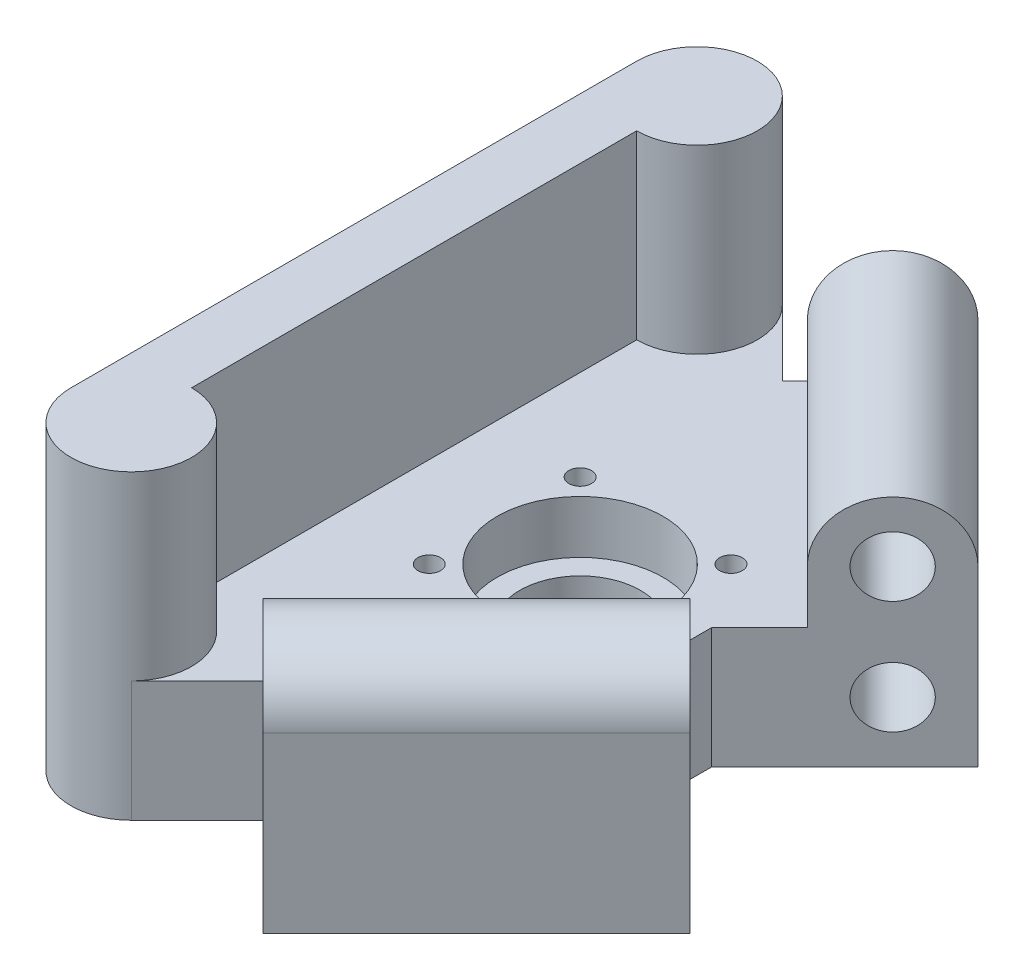
SolidWorks part; units mm, degrees
material "ABS"
ref_plane "Front Plane" through (0, 0, 0) normal (0, 0, 1) x (1, 0, 0)
ref_plane "Top Plane" through (0, 0, 0) normal (0, 1, 0) x (1, 0, 0)
ref_plane "Right Plane" through (0, 0, 0) normal (1, 0, 0) x (0, 0, -1)
sketch "Sketch1" plane through (0, 0, 0) normal (0, 1, 0) x (1, 0, 0)
  line L0 (-386.3027, 0) -> (412.614, 0) construction
  line L1 (0, -323.8826) -> (0, 265.8262) construction
  line L2 (0, 251.091) -> (251.091, 0)
  line L3 (160, 0) -> (80, 138.5641)
  line L4 (160, 0) -> (0, 0)
  line L5 (0, 239.7773) -> (239.7773, 0)
  line L6 (196.4046, 34.4091) -> (187.6569, 43.1569)
  line L9 (174, 0) -> (174, 37.5)
  line L11 (196.4046, 34.4091) -> (209.3717, 47.3762)
  line L12 (209.3717, 47.3762) -> (237.6559, 19.0919)
  line L13 (237.6559, 19.0919) -> (220, 1.4359)
  line L14 (220, 1.4359) -> (220, -1.4359)
  line L15 (237.6559, -19.0919) -> (220, -1.4359)
  line L16 (209.3717, -47.3762) -> (237.6559, -19.0919)
  line L17 (196.4046, -34.4091) -> (209.3717, -47.3762)
  line L18 (187.6569, -43.1569) -> (196.4046, -34.4091)
  line L19 (174, 0) -> (174, -37.5)
  circle A0 centre (0, 0) radius 160
  circle A6 centre (204, 0) radius 11
  circle A7 centre (182, 37.5) radius 4
  circle A8 centre (80, 138.5641) radius 15
  circle A9 centre (194, 10) radius 1.5
  circle A10 centre (214, 10) radius 1.5
  circle A11 centre (214, -10) radius 1.5
  circle A12 centre (194, -10) radius 1.5
  arc A14 (174, 37.5) -> (187.6569, 43.1569) centre (182, 37.5) cw
  circle A16 centre (182, -37.5) radius 4
  arc A17 (174, -37.5) -> (187.6569, -43.1569) centre (182, -37.5) ccw
  circle A21 centre (204, 0) radius 8
  point P53 (220, 0)
  point P65 (144, 0)
  dimension "D1" = 320
  dimension "D10" = 22
  dimension "D13" = 30
  dimension "D11" = 8
  dimension "D14" = 8
  dimension "D18" = 3
  dimension "D28" = 8
  dimension "D34" = 16
  dimension "D8" = 45
  dimension "D9" = 160
  dimension "D12" = 37.5
  dimension "D15" = 15
  dimension "D16" = 44
  dimension "D17" = 22
  dimension "D19" = 10
  dimension "D20" = 10
  dimension "D26" = 8
  dimension "D29" = 4
  dimension "D31" = 16
  dimension "D32" = 40
  dimension "D21" = 2
  dimension "D22" = 2
extrude "Boss-Extrude1" add sketch "Sketch1" along normal blind 16 contours L19 A17 L18 L17 L16 L15 L14 L13 L5 L11 A14 L9 A0 A16 A12 A11 A10 A9 A7 A6 | L13 L2 L11 L5 | L13 L12 L11 L2 | A7 | A16 region at (222.0996, 0, -31.8198) region at (217.857, 0, -27.5772) region at (214.2324, 0, -23.9526) region at (182, 0, -37.5) region at (182, 0, 37.5)
extrude "Boss-Extrude2" add sketch "Sketch1<4>" along normal blind 9 contours A6 A21 region at (193.3111, 0, 0)
sketch "Sketch1<4>" plane through (0, 0, 0) normal (0, 1, 0) x (1, 0, 0) same geometry as "Sketch1"
sketch "Sketch2" plane through (109.282, 0, 109.282) normal (0.7071, 0, 0.7071) x (0.7071, 0, -0.7071)
  line L0 (181.5481, 16) -> (156.5789, 16) construction
  line L1 (181.5481, 16) -> (181.5481, 0) construction
  circle A0 centre (173.5481, 8) radius 4
  dimension "D1" = 8
  dimension "D2" = 8
  dimension "D3" = 8
extrude "Cut-Extrude1" cut sketch "Sketch2" against normal through all
sketch "Sketch3" plane through (109.282, 0, -109.282) normal (0.7071, 0, -0.7071) x (-0.7071, 0, -0.7071)
  line L0 (-181.5481, 16) -> (-181.5481, 0) construction
  line L1 (-181.5481, 0) -> (-156.5789, 0) construction
  circle A0 centre (-173.5481, 8) radius 4
  dimension "D1" = 8
  dimension "D2" = 8
  dimension "D3" = 8
extrude "Cut-Extrude2" cut sketch "Sketch3" against normal through all
sketch "Sketch4" plane through (0, 0, 0) normal (0, -1, 0) x (1, 0, 0)
  line L25 (197.4641, 10) -> (195.7321, 13)
  line L26 (195.7321, 13) -> (192.2679, 13)
  line L27 (192.2679, 13) -> (190.5359, 10)
  line L28 (190.5359, 10) -> (192.2679, 7)
  line L29 (192.2679, 7) -> (195.7321, 7)
  line L30 (195.7321, 7) -> (197.4641, 10)
  line L31 (217.4641, 10) -> (215.7321, 13)
  line L32 (215.7321, 13) -> (212.2679, 13)
  line L33 (212.2679, 13) -> (210.5359, 10)
  line L34 (210.5359, 10) -> (212.2679, 7)
  line L35 (212.2679, 7) -> (215.7321, 7)
  line L36 (215.7321, 7) -> (217.4641, 10)
  line L37 (197.4641, -10) -> (195.7321, -7)
  line L38 (195.7321, -7) -> (192.2679, -7)
  line L39 (192.2679, -7) -> (190.5359, -10)
  line L40 (190.5359, -10) -> (192.2679, -13)
  line L41 (192.2679, -13) -> (195.7321, -13)
  line L42 (195.7321, -13) -> (197.4641, -10)
  line L43 (217.4641, -10) -> (215.7321, -7)
  line L44 (215.7321, -7) -> (212.2679, -7)
  line L45 (212.2679, -7) -> (210.5359, -10)
  line L46 (210.5359, -10) -> (212.2679, -13)
  line L47 (212.2679, -13) -> (215.7321, -13)
  line L48 (215.7321, -13) -> (217.4641, -10)
  circle A4 centre (194, 10) radius 3 construction
  circle A5 centre (214, 10) radius 3 construction
  circle A6 centre (194, -10) radius 3 construction
  circle A7 centre (214, -10) radius 3 construction
extrude "Cut-Extrude3" cut sketch "Sketch4" against normal blind 2.5
sketch "Sketch5" plane through (80.9978, 0, -80.9978) normal (-0.7071, 0, 0.7071) x (0.7071, 0, 0.7071)
  line L0 (181.5481, 16) -> (181.5481, 23)
  line L1 (165.5481, 23) -> (165.5481, 16)
  line L2 (163.2099, 16) -> (181.5481, 16) construction
  line L3 (165.5481, 16) -> (181.5481, 16)
  circle A0 centre (173.5481, 23) radius 4
  circle A1 centre (173.5481, 8) radius 4 construction
  arc A2 (181.5481, 23) -> (165.5481, 23) centre (173.5481, 23) ccw
  dimension "D1" = 8
  dimension "D3" = 8
  dimension "D2" = 15
sketch "Sketch6" plane through (80.9978, 0, 80.9978) normal (-0.7071, 0, -0.7071) x (-0.7071, 0, 0.7071)
  line L0 (-165.5481, 16) -> (-165.5481, 23)
  line L1 (-181.5481, 23) -> (-181.5481, 16)
  line L2 (-181.5481, 16) -> (-165.5481, 16)
  circle A0 centre (-173.5481, 23) radius 4
  arc A1 (-165.5481, 23) -> (-181.5481, 23) centre (-173.5481, 23) ccw
  circle A2 centre (-173.5481, 8) radius 4 construction
  dimension "D1" = 8
  dimension "D2" = 8
  dimension "D3" = 15
extrude "Boss-Extrude4" add sketch "Sketch5" against normal up to surface (40 mm away) up to face at (229.1707, 8, 10.6066)
extrude "Boss-Extrude5" add sketch "Sketch6" against normal up to surface (40 mm away) up to face at (234.8275, 8, -16.2635)
sketch "Sketch7" plane through (0, 0, 0) normal (0, 1, 0) x (1, 0, 0)
  line L0 (174, -37.5) -> (174, 37.5)
  line L1 (182, 29.5) -> (182, -29.5)
  circle A0 centre (182, 37.5) radius 8
  circle A1 centre (182, -37.5) radius 8
  arc A2 (174, -37.5) -> (187.6569, -43.1569) centre (182, -37.5) ccw construction
  arc A3 (187.6569, 43.1569) -> (174, 37.5) centre (182, 37.5) ccw construction
extrude "Boss-Extrude6" add sketch "Sketch7" along normal blind 40 contours A1 A0 L0 | A1 | A0 region at (177.8783, 0, 0) region at (182, 0, 37.5)
ref_axis "Axis1" through (204, 9, 0) along (0, -1, 0)
extrude "Cut-Extrude4" cut sketch "Sketch1<6>" along normal blind 28 contours A16 | A7 region at (182, 0, -37.5) region at (182, 0, 37.5)
sketch "Sketch1<6>" plane through (0, 0, 0) normal (0, 1, 0) x (1, 0, 0) same geometry as "Sketch1"
equation "\"rod_diameter\"= 8"
equation "\"rod_hole_thickness\"= 4"
equation "\"rod_radius\"= \"rod_diameter\" / 2"
equation "\"platter_diameter\"= 320"
equation "\"platter_radius\"= \"platter_diameter\" / 2"
equation "\"extruder_mount_hole_spacing\"= 75"
equation "\"arm_rod_spacing\"= 40"
equation "\"D1@Sketch1\"=\"platter_diameter\""
equation "\"D9@Sketch1\"=\"platter_radius\""
equation "\"D11@Sketch1\"=\"rod_diameter\""
equation "\"D14@Sketch1\"=\"rod_diameter\""
equation "\"D12@Sketch1\"=\"z_rod_spacing\"/2"
equation "\"D26@Sketch1\"=\"rod_radius\"+\"rod_hole_thickness\""
equation "\"D28@Sketch1\"=\"rod_radius\"+\"rod_hole_thickness\""
equation "\"D29@Sketch1\"=\"rod_hole_thickness\""
equation "\"D1@Boss-Extrude2\"= \"D1@Boss-Extrude1\" - 7"
equation "\"D1@Sketch2\" = \"rod_diameter\""
equation "\"D2@Sketch2\"= \"D1@Boss-Extrude1\" / 2"
equation "\"D3@Sketch2\"=\"rod_radius\"+\"rod_hole_thickness\""
equation "\"D1@Sketch3\"=\"rod_diameter\""
equation "\"D2@Sketch3\"=\"rod_radius\"+\"rod_hole_thickness\""
equation "\"D3@Sketch3\"= \"D1@Boss-Extrude1\" / 2"
equation "\"D1@Boss-Extrude1\" = \"rod_diameter\" + \"rod_hole_thickness\" * 2"
equation "\"D1@Sketch5\" = \"rod_diameter\""
equation "\"top_frame_rod_spacing\"= \"arm_rod_spacing\" + 40"
equation "\"motor_level_rod_spacing\"= 15"
equation "\"D2@Sketch5\"=\"motor_level_rod_spacing\""
equation "\"D3@Sketch5\"=\"rod_radius\"+\"rod_hole_thickness\""
equation "\"D3@Sketch6\"=\"motor_level_rod_spacing\""
equation "\"D1@Sketch6\"=\"rod_diameter\""
equation "\"D2@Sketch6\"=\"rod_radius\"+\"rod_hole_thickness\""
equation "\"linear_bearing_diameter\"= 15"
equation "\"platter_rod_spacing\"= 50"
equation "\"z_rod_spacing\"= 75"
